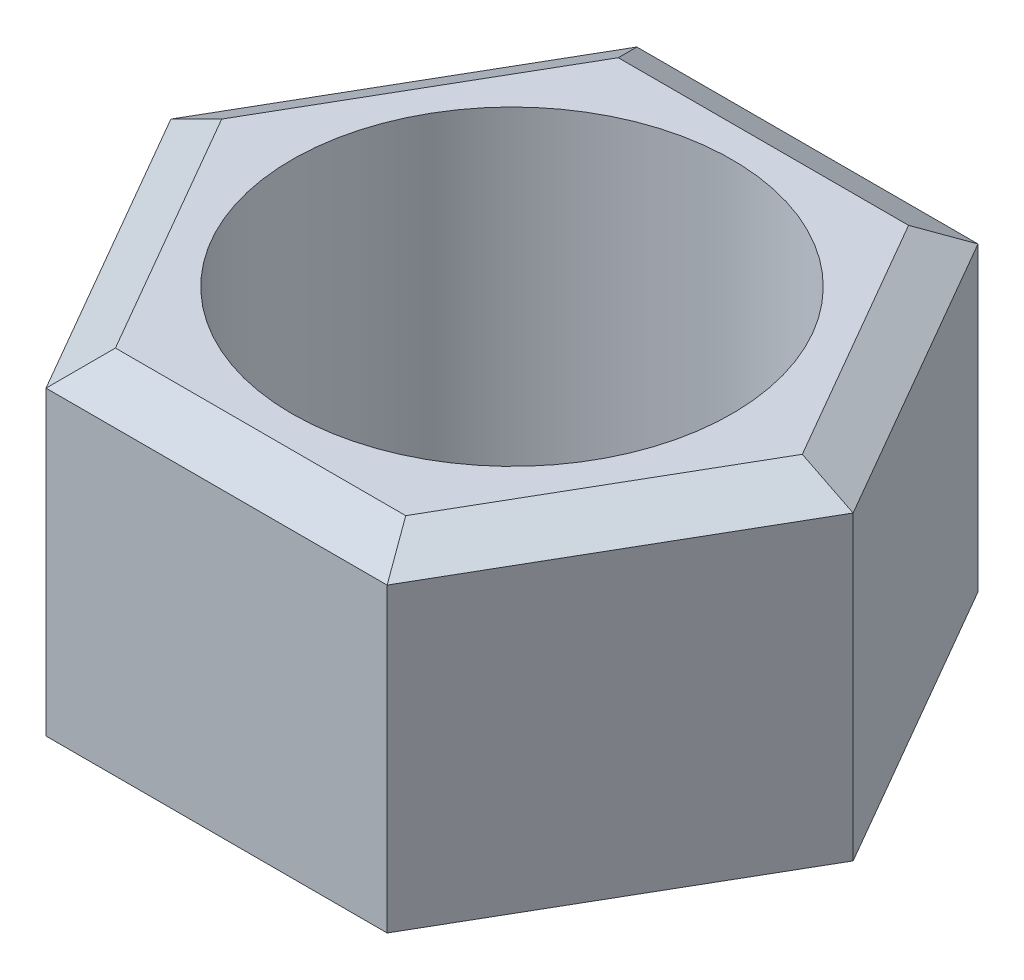
SolidWorks part; units mm, degrees
ref_plane "Спереди" through (0, 0, 0) normal (0, 0, 1) x (1, 0, 0)
ref_plane "Сверху" through (0, 0, 0) normal (0, 1, 0) x (1, 0, 0)
ref_plane "Справа" through (0, 0, 0) normal (1, 0, 0) x (0, 0, -1)
sketch "Эскиз1" plane through (0, 0, 0) normal (0, 1, 0) x (1, 0, 0)
  line L1 (-7.75, 0) -> (-3.875, -6.7117)
  line L2 (-3.875, -6.7117) -> (3.875, -6.7117)
  line L3 (3.875, -6.7117) -> (7.75, 0)
  line L4 (7.75, 0) -> (3.875, 6.7117)
  line L5 (3.875, 6.7117) -> (-3.875, 6.7117)
  line L6 (-3.875, 6.7117) -> (-7.75, 0)
  circle A0 centre (0, 0) radius 7.75 construction
  circle A1 centre (0, 0) radius 5
extrude "Бобышка-Вытянуть1" add sketch "Эскиз1" along normal blind 8
chamfer "Фаска1" distance 1 angle 30 6 edges at (5.8125, 8, -3.3558) (0, 8, -6.7117) (-5.8125, 8, -3.3558) (-5.8125, 8, 3.3558) (0, 8, 6.7117) (5.8125, 8, 3.3558) first distance on face at (0, 8, 0)
chamfer "Фаска2" distance 1 angle 30 6 edges at (-5.8125, 0, -3.3558) (-5.8125, 0, 3.3558) (0, 0, 6.7117) (5.8125, 0, 3.3558) (5.8125, 0, -3.3558) (0, 0, -6.7117) first distance on face at (0, 0, 0)
